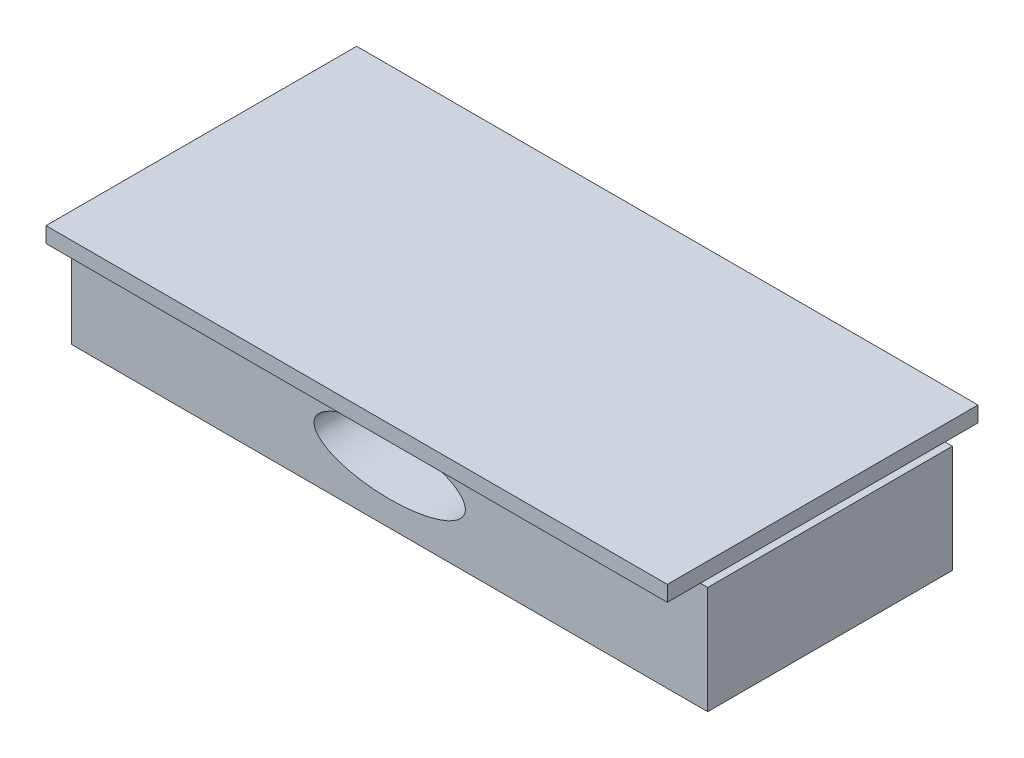
SolidWorks part; units mm, degrees
ref_plane "Front Plane" through (0, 0, 0) normal (0, 0, 1) x (1, 0, 0)
ref_plane "Top Plane" through (0, 0, 0) normal (0, 1, 0) x (1, 0, 0)
ref_plane "Right Plane" through (0, 0, 0) normal (1, 0, 0) x (0, 0, -1)
sketch "Sketch1" plane through (0, 0, 0) normal (0, 1, 0) x (1, 0, 0)
  line L1 (-65, -25) -> (65, -25)
  line L2 (-65, -25) -> (-65, 25)
  line L3 (-65, 25) -> (65, 25)
  line L4 (65, -25) -> (65, 25)
  line L5 (0, 25) -> (0, -25) construction
  line L6 (-65, 0) -> (65, 0) construction
  point P0 (0, 0)
  dimension "D1" = 130
  dimension "D2" = 50
extrude "Boss-Extrude1" add sketch "Sketch1" along normal blind 22
sketch "Sketch2" plane through (0, 0, 25) normal (0, 0, 1) x (1, 0, 0)
  ellipse E0 centre (0, 11) end of major axis (15.4617, 11) minor radius 5.8847
extrude "Cut-Extrude1" cut sketch "Sketch2" against normal through all
sketch "Sketch3" plane through (0, 22, 0) normal (0, 1, 0) x (1, 0, 0)
  line L1 (-63.5, -31.75) -> (63.5, -31.75)
  line L2 (-63.5, -31.75) -> (-63.5, 31.75)
  line L3 (-63.5, 31.75) -> (63.5, 31.75)
  line L4 (63.5, -31.75) -> (63.5, 31.75)
  line L5 (0, 31.75) -> (0, -31.75) construction
  line L6 (-63.5, 0) -> (63.5, 0) construction
  point P0 (0, 0)
  dimension "D1" = 127
  dimension "D2" = 63.5
extrude "Boss-Extrude2" add sketch "Sketch3" along normal blind 3.175
